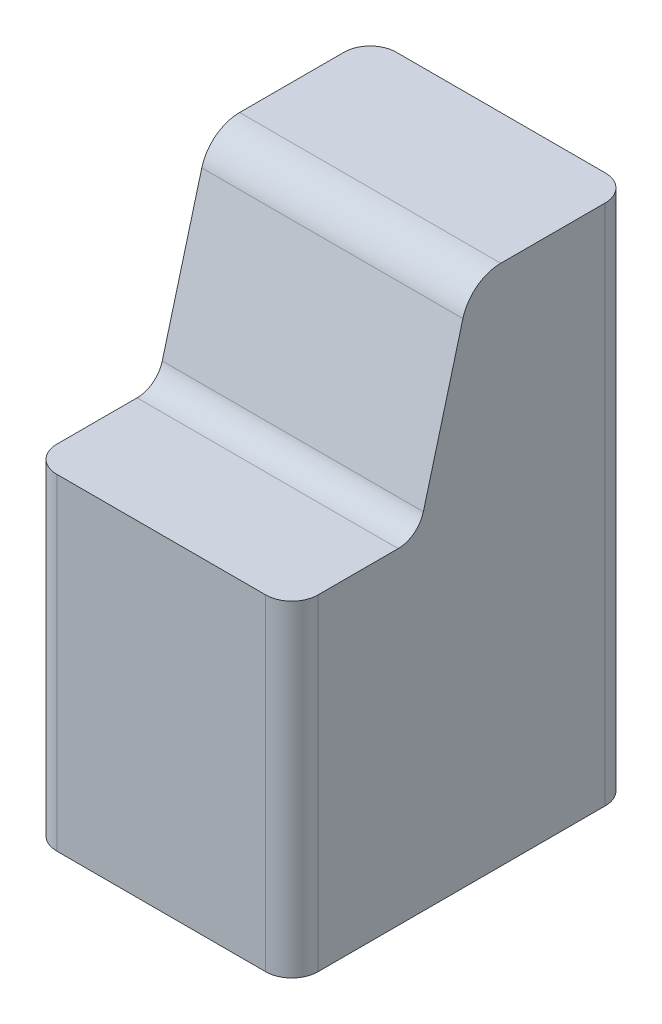
SolidWorks part; units mm, degrees
material "K110"
ref_plane "Front Plane" through (0, 0, 0) normal (0, 0, 1) x (1, 0, 0)
ref_plane "Top Plane" through (0, 0, 0) normal (0, 1, 0) x (1, 0, 0)
ref_plane "Right Plane" through (0, 0, 0) normal (1, 0, 0) x (0, 0, -1)
sketch "Sketch1" plane through (0, 0, 0) normal (1, 0, 0) x (0, 0, -1)
  line L0 (-10, 0) -> (0, 0)
  line L1 (0, 0) -> (0, -40)
  line L2 (0, -40) -> (-26, -40)
  line L3 (-26, -40) -> (-26, -15)
  line L4 (-26, -15) -> (-16.3212, -15)
  line L5 (-16.3212, -15) -> (-12.8978, -2.2235)
  arc A0 (-12.8978, -2.2235) -> (-10, 0) centre (-10, -3) cw
  dimension "D2" = 3
  dimension "D1" = 10
  dimension "D3" = 40
  dimension "D4" = 25
  dimension "D5" = 75
  dimension "D6" = 26
extrude "Boss-Extrude1" add sketch "Sketch1" along normal mid plane 20
fillet "Fillet1" radius 2 4 edges at (-10, -20, 0) (-10, -27.5, 26) (10, -20, 0) (10, -27.5, 26)
hole_wizard "M6 Tapped Hole1" positions "Sketch4" profile "Sketch3" tap size "M6" standard "ISO"
sketch "Sketch4" plane through (0, -40, 0) normal (0, -1, 0) x (-1, 0, 0)
  line L0 (-8, 0) -> (8, 0) construction
  point P0 (0, -7.5)
  point P14 (0, 0)
  dimension "D1" = 7.5
sketch "Sketch3" plane through (0, -40, 7.5) normal (1, 0, 0) x (0, 0, -1)
  line L0 (0, 0) -> (0, 18.5022)
  line L1 (0, 18.5022) -> (2.5, 17)
  line L2 (2.5, 17) -> (2.5, 0.525)
  line L3 (2.5, 0.525) -> (3.025, 0)
  line L5 (3.025, 0) -> (0, 0)
  line L6 (-2.5, 0.525) -> (-3.025, 0) construction
  line L10 (0, 18.5022) -> (-2.5, 17) construction
  line L11 (0, -6.35) -> (0, 107.95) construction
  dimension "Tap Drill Dia." = 5
  dimension "Tap Drill Depth" = 17
  dimension "Near C'Sink Dia." = 6.05
  dimension "Near C'Sink Angle" = 90
  dimension "Drill Angle" = 118
cosmetic thread "Hole Thread2" parameters "D1"=12, "D2"=6
fillet "Fillet2" radius 2 1 edges at (0, -15, 16.3212)
